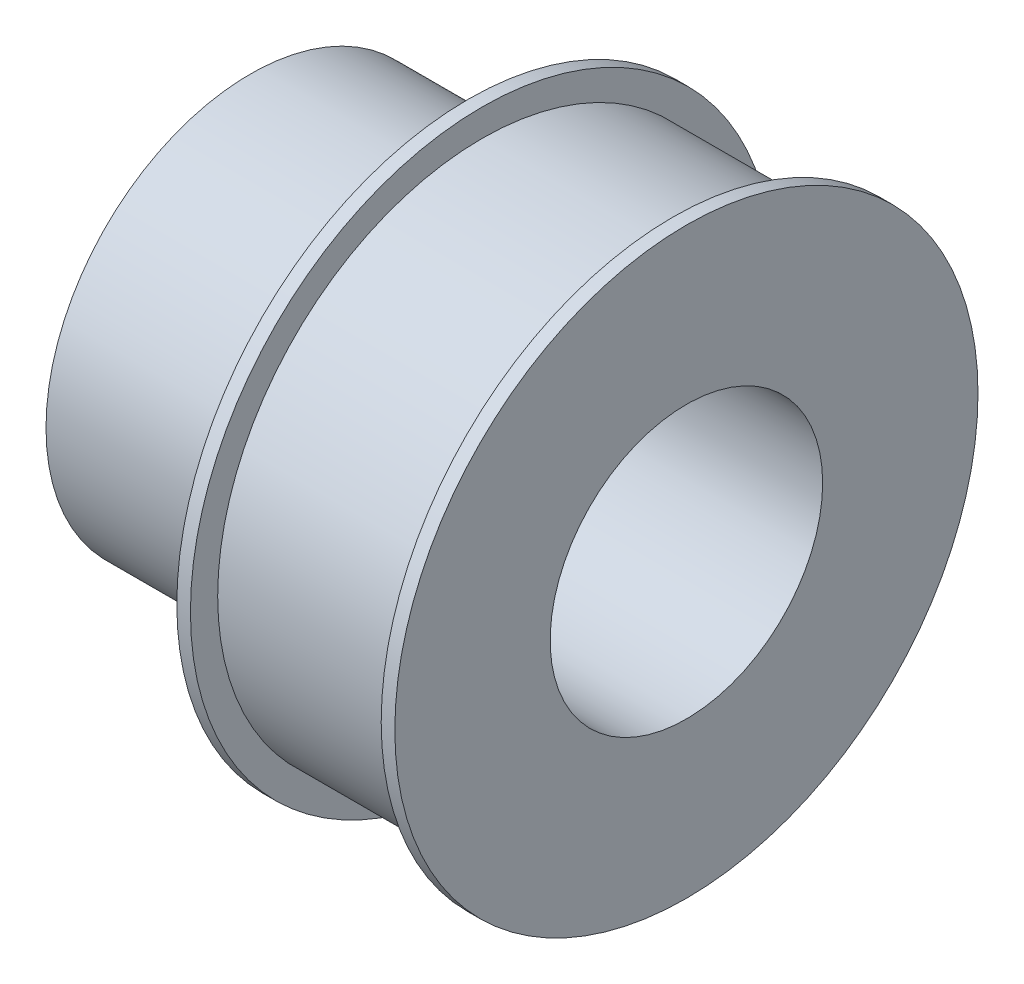
SolidWorks part; units mm, degrees
ref_plane "前视基准面" through (0, 0, 0) normal (0, 0, 1) x (1, 0, 0)
ref_plane "上视基准面" through (0, 0, 0) normal (0, 1, 0) x (1, 0, 0)
ref_plane "右视基准面" through (0, 0, 0) normal (1, 0, 0) x (0, 0, -1)
sketch "草图1" plane through (0, 0, 0) normal (1, 0, 0) x (0, 0, -1)
  circle A0 centre (0, 0) radius 9.7
  dimension "D1" = 19.4
extrude "凸台-拉伸1" add sketch "草图1" along normal blind 7
sketch "草图2" plane through (0, 0, 0) normal (-1, 0, 0) x (0, 0, 1)
  circle A0 centre (0, 0) radius 10.7
  circle A1 centre (0, 0) radius 9.7 construction
  dimension "D1" = 1
extrude "凸台-拉伸2" add sketch "草图2" along normal blind 0.5
sketch "草图3" plane through (7, 0, 0) normal (1, 0, 0) x (0, 0, -1)
  circle A0 centre (0, 0) radius 10.7
extrude "凸台-拉伸3" add sketch "草图3" along normal blind 0.5
sketch "草图4" plane through (-0.5, 0, 0) normal (-1, 0, 0) x (0, 0, 1)
  circle A0 centre (0, 0) radius 5
  dimension "D1" = 10
extrude "切除-拉伸1" cut sketch "草图4" against normal blind 14.5
sketch "草图5" plane through (-0.5, 0, 0) normal (-1, 0, 0) x (0, 0, 1)
  circle A0 centre (0, 0) radius 5 construction
  circle A1 centre (0, 0) radius 5
  circle A2 centre (0, 0) radius 7.5
  dimension "D1" = 15
extrude "凸台-拉伸4" add sketch "草图5" along normal offset from surface (8 mm away) 16 up to face at (7.5, 0, -5)
